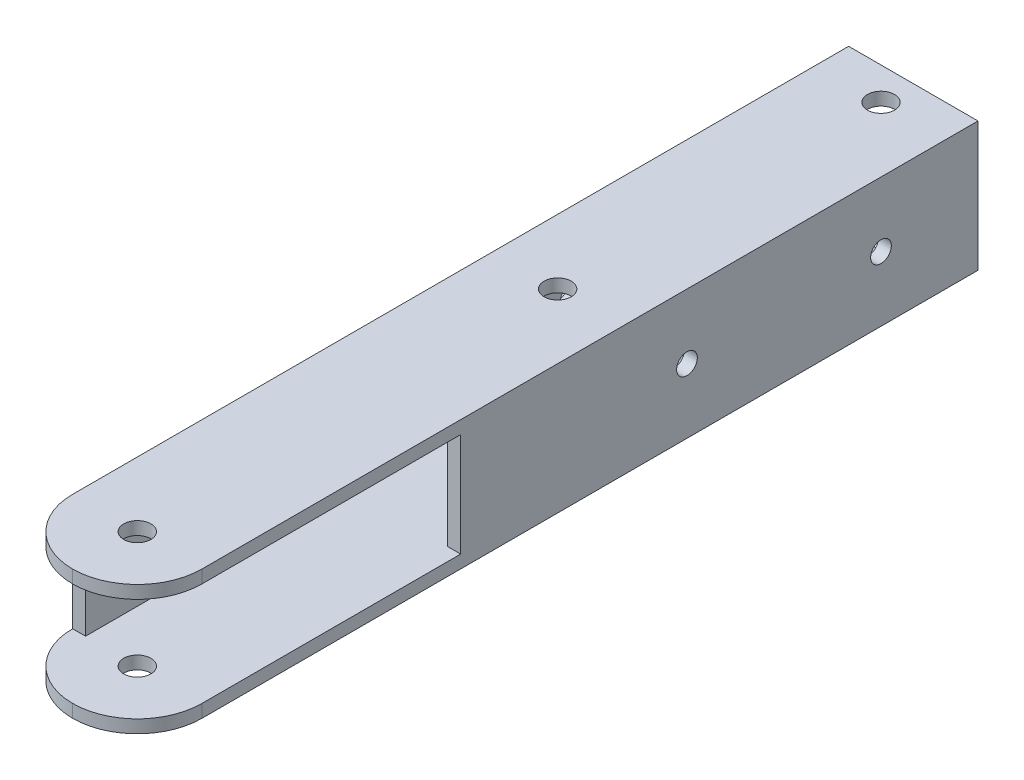
SolidWorks part; units mm, degrees
ref_plane "正面" through (0, 0, 0) normal (0, 0, 1) x (1, 0, 0)
ref_plane "平面" through (0, 0, 0) normal (0, 1, 0) x (1, 0, 0)
ref_plane "右側面" through (0, 0, 0) normal (1, 0, 0) x (0, 0, -1)
sketch "ｽｹｯﾁ1" plane through (0, 0, 0) normal (0, 0, 1) x (1, 0, 0)
  line L0 (-8, 8) -> (-8, -8)
  line L1 (-10, 10) -> (10, 10)
  line L2 (-10, 10) -> (-10, -10)
  line L3 (-10, -10) -> (10, -10)
  line L4 (10, 10) -> (10, -10)
  line L5 (-10, 10) -> (10, -10) construction
  line L6 (-10, -10) -> (10, 10) construction
  line L7 (-8, -8) -> (8, -8)
  line L8 (8, 8) -> (8, -8)
  line L9 (-8, 8) -> (8, 8)
  point P0 (0, 0)
  dimension "D1" = 20
  dimension "D2" = 20
  dimension "D3" = 2
extrude "ﾎﾞｽ - 押し出し1" add sketch "ｽｹｯﾁ1" along normal blind 130
sketch "ｽｹｯﾁ2" plane through (0, 10, 0) normal (0, 1, 0) x (1, 0, 0)
  line L0 (10, -130) -> (-10, -130) construction
  line L1 (10, 0) -> (-10, 0) construction
  circle A0 centre (0, -5) radius 2.1
  circle A1 centre (0, -55) radius 2.1
  circle A2 centre (0, -120) radius 2.1
  dimension "D1" = 55
  dimension "D2" = 4.2
  dimension "D3" = 5
  dimension "D4" = 4.2
  dimension "D5" = 10
  dimension "D6" = 4.2
extrude "ｶｯﾄ - 押し出し1" cut sketch "ｽｹｯﾁ2" against normal blind 408.3717
sketch "ｽｹｯﾁ3" plane through (10, 0, 0) normal (1, 0, 0) x (0, 0, -1)
  line L1 (0, -10) -> (0, 10) construction
  circle A0 centre (-15, 0) radius 1.6
  circle A1 centre (-45, 0) radius 1.6
  dimension "D1" = 3.2
  dimension "D2" = 3.2
  dimension "D3" = 45
  dimension "D4" = 15
extrude "ｶｯﾄ - 押し出し2" cut sketch "ｽｹｯﾁ3" against normal through all
sketch "ｽｹｯﾁ5" plane through (10, 0, 0) normal (1, 0, 0) x (0, 0, -1)
  line L0 (-130, -10) -> (-130, 10) construction
  line L1 (-130, -8) -> (-80, -8)
  line L2 (-130, -8) -> (-130, 8)
  line L3 (-130, 8) -> (-80, 8)
  line L4 (-80, -8) -> (-80, 8)
  line L5 (-130, -10) -> (0, -10) construction
  line L6 (-130, 10) -> (0, 10) construction
  dimension "D1" = 50
  dimension "D2" = 2
  dimension "D3" = 2
extrude "ｶｯﾄ - 押し出し3" cut sketch "ｽｹｯﾁ5" against normal through all
sketch "ｽｹｯﾁ6" plane through (-10, 0, 0) normal (-1, 0, 0) x (0, 0, 1)
  line L0 (130, -8) -> (80, -8) construction
  line L1 (80, 8) -> (120, 8)
  line L2 (80, 8) -> (80, -8)
  line L3 (80, -8) -> (120, -8)
  line L4 (120, 8) -> (120, -8)
  line L6 (80, -8) -> (80, 8) construction
  dimension "D1" = 40
  dimension "D2" = 0
extrude "ﾎﾞｽ - 押し出し2" add sketch "ｽｹｯﾁ6" against normal blind 2
fillet "ﾌｨﾚｯﾄ1" radius 10 4 edges at (-10, 9, 130) (10, 9, 130) (10, -9, 130) (-10, -9, 130)
